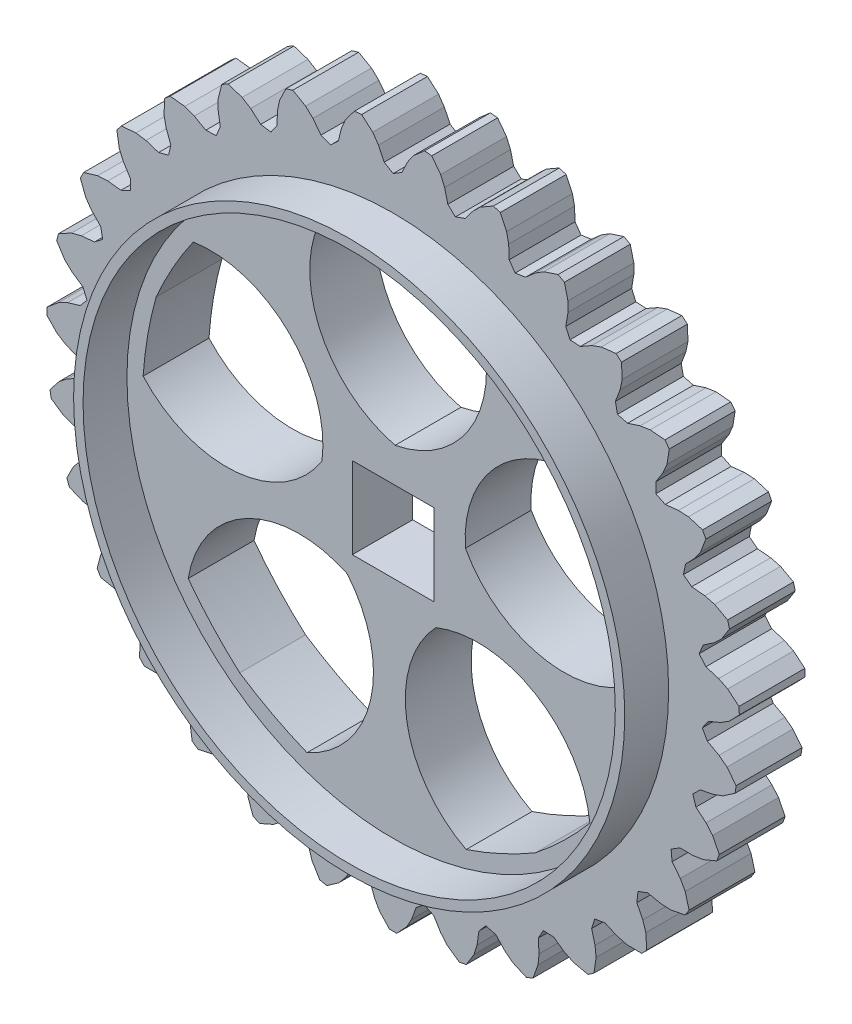
SolidWorks part; units mm, degrees
ref_plane "Front Plane" through (0, 0, 0) normal (0, 0, 1) x (1, 0, 0)
ref_plane "Top Plane" through (0, 0, 0) normal (0, 1, 0) x (1, 0, 0)
ref_plane "Right Plane" through (0, 0, 0) normal (1, 0, 0) x (0, 0, -1)
sketch "Sketch1" plane through (0, 0, 0) normal (0, 0, 1) x (1, 0, 0)
  line L1 (3.7123, -3.7123) -> (-3.7123, -3.7123)
  line L2 (3.7123, -3.7123) -> (3.7123, 3.7123)
  line L3 (3.7123, 3.7123) -> (-3.7123, 3.7123)
  line L4 (-3.7123, -3.7123) -> (-3.7123, 3.7123)
  line L5 (3.7123, -3.7123) -> (-3.7123, 3.7123) construction
  line L6 (3.7123, 3.7123) -> (-3.7123, -3.7123) construction
  circle A0 centre (0, 0) radius 31.574
  circle A1 centre (0, 0) radius 5.25 construction
  dimension "D1" = 63.148
  dimension "D2" = 10.5
extrude "Boss-Extrude1" add sketch "Sketch1" along normal blind 6
sketch "Sketch2" plane through (0, 0, 0) normal (0, 0, 1) x (1, 0, 0)
  line L0 (0, 0) -> (0, 32.8121) construction
  line L1 (0, 28.214) -> (-0.8069, 28.7123)
  line L2 (-0.8069, 28.7123) -> (-1.33, 29.8022)
  line L3 (-1.33, 29.8022) -> (-1.8557, 30.5578)
  line L4 (-1.8557, 30.5578) -> (-2.8665, 31.4436)
  line L5 (-2.8665, 31.4436) -> (-1.8557, 32.2161)
  line L6 (-1.8557, 32.2161) -> (0, 32.8121)
  line L7 (1.8557, 32.2161) -> (0, 32.8121)
  line L8 (2.8665, 31.4436) -> (1.8557, 32.2161)
  line L9 (1.8557, 30.5578) -> (2.8665, 31.4436)
  line L10 (1.33, 29.8022) -> (1.8557, 30.5578)
  line L11 (0.8069, 28.7123) -> (1.33, 29.8022)
  line L12 (0, 28.214) -> (0.8069, 28.7123)
  circle A22 centre (0, 0) radius 31.574 construction
  dimension "D5" = 0.5258
  dimension "D6" = 0.7556
  dimension "D9" = 0.5959
  dimension "D1" = 0.8069
  dimension "D2" = 0.4984
  dimension "D3" = 0.5231
  dimension "D4" = 1.0898
  dimension "D7" = 0.8858
  dimension "D8" = 1.8557
  dimension "D10" = 1.0107
  dimension "D11" = 0.7725
  dimension "D12" = 1.0107
extrude "Cut-Extrude1" cut sketch "Sketch2" along normal through all
pattern_circular "CirPattern1" count 31 over 360 about axis through (0, 0, 6) along (0, 0, -1) of "Cut-Extrude1"
sketch "Sketch3" plane through (0, 0, 0) normal (0, 0, 1) x (1, 0, 0)
  circle A0 centre (0, 0) radius 29.75
  dimension "D1" = 59.5
sketch "Sketch4" plane through (0, 0, 0) normal (0, 0, 1) x (1, 0, 0)
  line L0 (0, 0) -> (0.6245, 22.9095) construction
  arc A0 (0.1872, 6.8675) -> (-6.2369, 21.9201) centre (2.6671, 16.823) cw
  arc A1 (0.6245, 22.9095) -> (-6.2369, 21.9201) centre (2.0438, -11.2177) ccw
  arc A2 (0.6245, 22.9095) -> (7.4217, 21.5478) centre (-2.6519, -11.0897) cw
  arc A3 (0.1872, 6.8675) -> (7.4217, 21.5478) centre (-1.7467, 16.9433) ccw
extrude "Cut-Extrude2" cut sketch "Sketch4" along normal through all both
sketch "Sketch5" plane through (0, 0, 0) normal (0, 0, 1) x (1, 0, 0)
  line L0 (3.7123, -3.7123) -> (-3.7123, 3.7123) construction
  circle A0 centre (0, 0) radius 25.1098
  circle A1 centre (0, 0) radius 24.2496
extrude "Boss-Extrude2" add sketch "Sketch5" along normal blind 10 separate body
pattern_circular "CirPattern2" count 5 over 360 about axis through (0, 0, 10) along (0, 0, -1) of "Cut-Extrude2" reverse direction yes
chamfer "Chamfer1" distance 0.5 angle 45 4 edges at (-3.7123, 0, 0) (0, -3.7123, 0) (3.7123, 0, 0) (0, 3.7123, 0)
